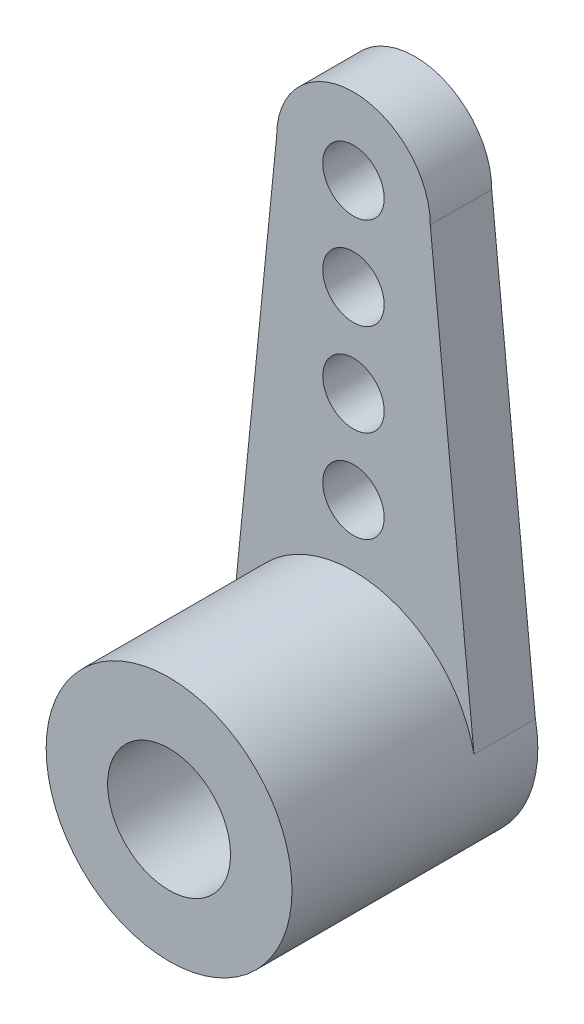
SolidWorks part; units mm, degrees
material "Nylon 101"
ref_plane "Piano frontale" through (0, 0, 0) normal (0, 0, 1) x (1, 0, 0)
ref_plane "Piano superiore" through (0, 0, 0) normal (0, 1, 0) x (1, 0, 0)
ref_plane "Piano destro" through (0, 0, 0) normal (1, 0, 0) x (0, 0, -1)
sketch "Schizzo1" plane through (0, 0, 0) normal (0, 0, 1) x (1, 0, 0)
  circle A1 centre (0, 0) radius 4
  dimension "D2" = 8
extrude "Estrusione-Estrusione1" add sketch "Schizzo1" along normal blind 8
shell "Svuota1" thickness 2 removed face at (4, 0, 8)
sketch "Schizzo3" plane through (0, 0, 0) normal (0, 0, -1) x (-1, 0, 0)
  circle A0 centre (0, 0) radius 14
  dimension "D1" = 28
extrude "Estrusione-Estrusione2" [suppressed] add sketch "Schizzo3" against normal blind 2
sketch "Schizzo5" plane through (0, 0, 0) normal (0, 0, -1) x (-1, 0, 0)
  line L0 (0, 0) -> (0, 15)
  line L1 (-2.5, 15) -> (-4, 0)
  line L2 (2.5, 15) -> (4, 0)
  circle A0 centre (0, 15) radius 2.5
  circle A1 centre (0, 0) radius 4 construction
  circle M3 centre (0, 0) radius 4
  dimension "D2" = 5
  dimension "D1" = 15
extrude "Estrusione-Estrusione3" add sketch "Schizzo5" against normal blind 2 contours A0 L0 L2 M3 | A0 L1 L0 M3 | A0 region at (1.73, 7.919, 0) region at (-1.73, 7.919, 0) region at (1.7178, 13.2822, 0)
sketch "Schizzo4" plane through (0, 0, 0) normal (0, 0, -1) x (-1, 0, 0)
  line L0 (0, 0) -> (0, 6)
  line L1 (0, 6) -> (0, 9)
  line L2 (0, 9) -> (0, 12)
  circle A0 centre (0, 6) radius 1
  circle A6 centre (0, 9) radius 1
  circle A7 centre (0, 12) radius 1
  circle A8 centre (0, 15) radius 1
  dimension "D6" = 2
  dimension "D1" = 6
  dimension "D2" = 4
extrude "Taglio-Estrusione2" cut sketch "Schizzo4" against normal up to next contours A0 | A6 | A7 | A8
sketch "Schizzo2" plane through (0, 0, 0) normal (0, 0, -1) x (-1, 0, 0)
  circle A0 centre (0, 0) radius 1.5
  dimension "D1" = 3
extrude "Taglio-Estrusione1" cut sketch "Schizzo2" against normal up to next and the other way blind 10
pattern_circular "RipetizioneCircolare1" [suppressed] count 4 over 360 of bodies 102
